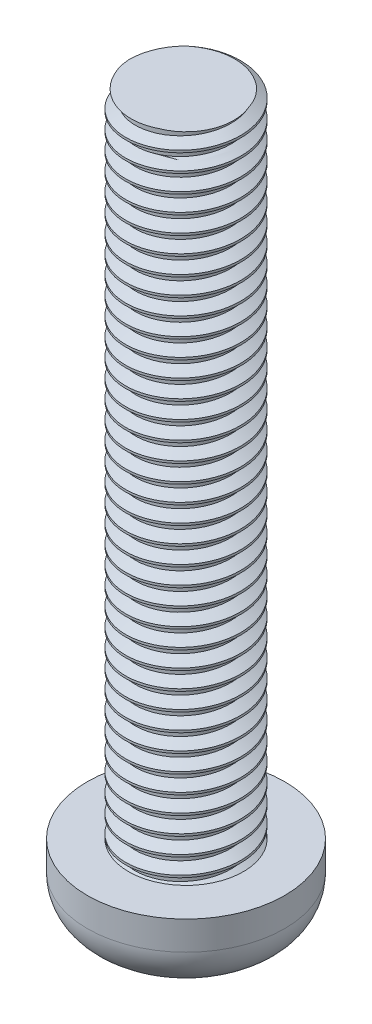
SolidWorks part; units mm, degrees
ref_plane "Płaszczyzna przednia" through (0, 0, 0) normal (0, 0, 1) x (1, 0, 0)
ref_plane "Płaszczyzna górna" through (0, 0, 0) normal (0, 1, 0) x (1, 0, 0)
ref_plane "Płaszczyzna prawa" through (0, 0, 0) normal (1, 0, 0) x (0, 0, -1)
sketch "Szkic1" plane through (0, 0, 0) normal (0, 1, 0) x (1, 0, 0)
  circle A0 centre (0, 0) radius 2.75
  dimension "D1" = 5.5
extrude "Dodanie-wyciągnięcie1" add sketch "Szkic1" along normal blind 2
sketch "Szkic2" plane through (0, 2, 0) normal (0, 1, 0) x (1, 0, 0)
  circle A0 centre (0, 0) radius 1.6
  dimension "D1" = 3.2
extrude "Dodanie-wyciągnięcie2" add sketch "Szkic2" along normal blind 18
thread "Gwint1" pitch 0.5 method cut profile "Profil gwintu1" start angle 0, offset 1, length 0, pitch 0.5, diameter 3.2
ref_plane "Płaszczyzna1" through (-1.6, 21, 0) normal (0, 0, 1) x (-1, 0, 0)
sketch "Profil gwintu1" plane through (-1.6, 21, 0) normal (0, 0, 1) x (-1, 0, 0)
  line L0 (0, 0) -> (0, 0.5) construction
  line L11 (0, 0) -> (0, 0.4375)
  line L12 (0, 0.4375) -> (-0.2706, 0.2812)
  line L13 (-0.2706, 0.2812) -> (-0.2706, 0.1562)
  line L15 (-0.2706, 0.1562) -> (0, 0)
  line L17 (-0.2706, 0.2187) -> (0, 0.2187) construction
  point P2 (0, 0)
  dimension "Pitch" = 0.5
  dimension "Profile_Angle" = 60
  dimension "Profile_Land" = 0.125
  dimension "Profile_Height" = 0.2706
fillet "Zaokrąglenie1" radius 1.2 1 edges at (0, 0, 2.75)
sketch "Szkic6" plane through (0, 0, 0) normal (0, -1, 0) x (1, 0, 0)
  line L0 (0, -1) -> (0, 1)
  line L1 (-1, 0) -> (1, 0)
  point P5 (0, 0)
  point P10 (0, 0)
  dimension "D1" = 2
  dimension "D2" = 2
extrude "Wycięcie-wyciągnięcie-cienka ścianka1" cut sketch "Szkic6" against normal blind 1 thin thin type mid plane wall 0.4
other "Menedżer właściwości PropertyManager" [suppressed]
